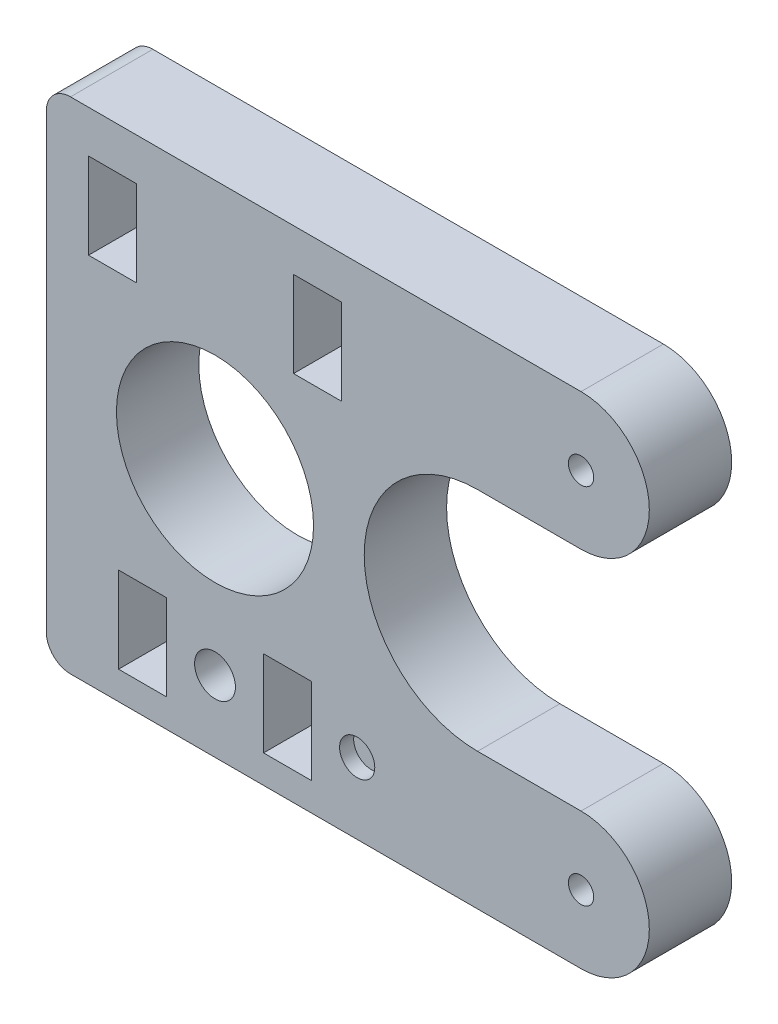
SolidWorks part; units mm, degrees
material "Acrylic (Medium-high impact)"
ref_plane "Front Plane" through (0, 0, 0) normal (0, 0, 1) x (1, 0, 0)
ref_plane "Top Plane" through (0, 0, 0) normal (0, 1, 0) x (1, 0, 0)
ref_plane "Right Plane" through (0, 0, 0) normal (1, 0, 0) x (0, 0, -1)
sketch "Sketch1" plane through (0, 0, 0) normal (0, 0, 1) x (1, 0, 0)
  line L0 (669.2168, 348.5155) -> (648.4638, 348.5155)
  line L1 (646.7465, 346.7982) -> (646.7465, 314.7328)
  line L2 (648.4638, 313.0155) -> (669.2168, 313.0155)
  line L3 (653.1465, 339.4155) -> (653.1465, 345.5155)
  line L4 (653.1465, 345.5155) -> (649.7465, 345.5155)
  line L5 (649.7465, 345.5155) -> (649.7465, 339.4155)
  line L6 (649.7465, 339.4155) -> (653.1465, 339.4155)
  line L7 (651.8765, 315.0155) -> (655.2765, 315.0155)
  line L8 (655.2765, 315.0155) -> (655.2765, 321.1155)
  line L9 (655.2765, 321.1155) -> (651.8765, 321.1155)
  line L10 (651.8765, 321.1155) -> (651.8765, 315.0155)
  line L11 (667.7065, 339.4155) -> (667.7065, 345.5155)
  line L12 (667.7065, 345.5155) -> (664.3065, 345.5155)
  line L13 (664.3065, 345.5155) -> (664.3065, 339.4155)
  line L14 (664.3065, 339.4155) -> (667.7065, 339.4155)
  line L15 (662.1765, 321.1155) -> (662.1765, 315.0155)
  line L16 (662.1765, 315.0155) -> (665.5765, 315.0155)
  line L17 (665.5765, 315.0155) -> (665.5765, 321.1155)
  line L18 (665.5765, 321.1155) -> (662.1765, 321.1155)
  line L19 (-318.4867, 330.7655) -> (49681.5133, 330.7655) construction
  line L21 (653.1465, 339.4155) -> (664.3065, 339.4155) construction
  line L22 (657.2765, 318.0655) -> (655.2765, 318.0655) construction
  line L23 (660.1765, 318.0655) -> (662.1765, 318.0655) construction
  line L24 (658.7265, -664.7806) -> (658.7265, 49335.2194) construction
  line L25 (669.2168, 313.0155) -> (684.7265, 313.0155)
  line L26 (669.2168, 348.5155) -> (684.7265, 348.5155)
  line L27 (684.7265, 317.8655) -> (684.7265, 330.7655) construction
  line L28 (684.7265, 330.7655) -> (684.7265, 343.6655) construction
  line L29 (684.7265, -669.3222) -> (684.7265, 49330.6778) construction
  line L30 (662.1765, 330.7655) -> (662.1765, 348.5155) construction
  line L31 (662.1765, 330.7655) -> (662.1765, 313.0155) construction
  line L32 (684.7265, 338.8155) -> (677.3765, 338.8155)
  line L33 (684.7265, 322.7155) -> (677.3765, 322.7155)
  circle A0 centre (684.7265, 343.6655) radius 0.9
  circle A1 centre (684.7265, 317.8655) radius 0.9
  arc A2 (684.7265, 313.0155) -> (684.7265, 322.7155) centre (684.7265, 317.8655) ccw
  circle A3 centre (658.7265, 318.0655) radius 1.45
  arc A4 (648.4638, 348.5155) -> (646.7465, 346.7982) centre (648.4638, 346.7982) ccw
  arc A5 (684.7265, 348.5155) -> (684.7265, 338.8155) centre (684.7265, 343.6655) cw
  arc A6 (677.3765, 338.8155) -> (677.3765, 322.7155) centre (677.3765, 330.7655) ccw
  arc A7 (646.7465, 314.7328) -> (648.4638, 313.0155) centre (648.4638, 314.7328) ccw
  circle A8 centre (658.7265, 330.7655) radius 7
  point P27 (658.7265, 339.4155)
  point P38 (669.3265, 330.7655)
  point P39 (665.7265, 330.7655)
  dimension "D5" = 2.9
  dimension "D12" = 3.6
  dimension "D13" = 14
  dimension "D14" = 1.8
  dimension "D15" = 1.7173
  dimension "D10" = 26
  dimension "D1" = 2
  dimension "D2" = 6.1
  dimension "D3" = 3.4
  dimension "D4" = 3.4
  dimension "D6" = 11.16
  dimension "D7" = 3
  dimension "D8" = 3
  dimension "D9" = 2
  dimension "D11" = 12.9
  dimension "D17" = 18.3
extrude "Boss-Extrude2" add sketch "Sketch1" along normal blind 5.85
sketch "Sketch2" plane through (0, 0, 5.85) normal (0, 0, 1) x (1, 0, 0)
  line L0 (-341.2735, 318.0655) -> (49658.7265, 318.0655) construction
  line L1 (665.5765, 315.0155) -> (665.5765, 321.1155) construction
  circle A0 centre (668.8265, 318.0655) radius 1.25
  point P5 (667.5765, 318.0655)
  dimension "D1" = 2.5
  dimension "D2" = 2
extrude "Cut-Extrude1" cut sketch "Sketch2" against normal blind 1
